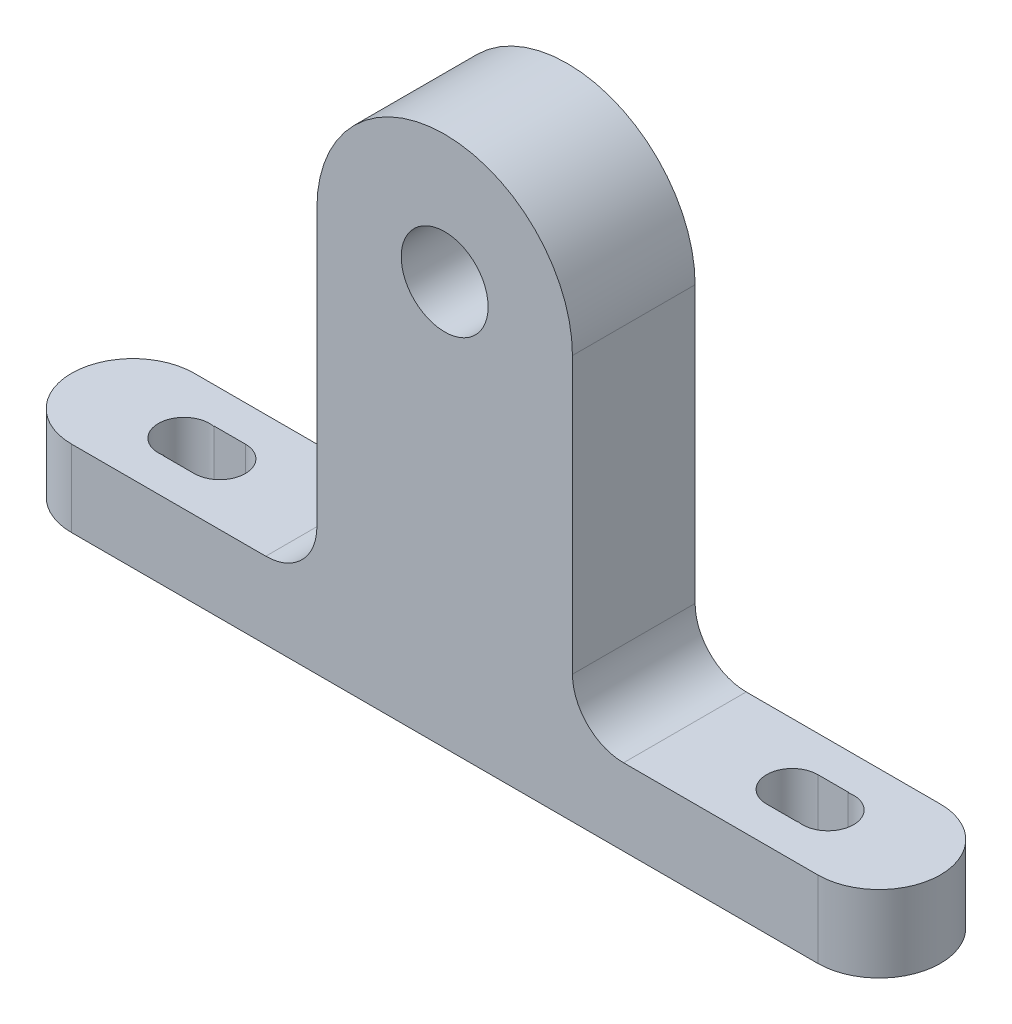
SolidWorks part; units mm, degrees
ref_plane "Front Plane" through (0, 0, 0) normal (0, 0, 1) x (1, 0, 0)
ref_plane "Top Plane" through (0, 0, 0) normal (0, 1, 0) x (1, 0, 0)
ref_plane "Right Plane" through (0, 0, 0) normal (1, 0, 0) x (0, 0, -1)
sketch "Sketch1" plane through (0, 0, 0) normal (0, 0, 1) x (1, 0, 0)
  line L0 (-42.5, -39.5) -> (42.5, -39.5)
  line L1 (42.5, -39.5) -> (42.5, -32)
  line L2 (42.5, -32) -> (12.5, -32)
  line L3 (12.5, -32) -> (12.5, 0)
  line L4 (-42.5, -39.5) -> (-42.5, -32)
  line L5 (-42.5, -32) -> (-12.5, -32)
  line L6 (-12.5, -32) -> (-12.5, 0)
  line L7 (0, -39.5) -> (0, 0) construction
  line L8 (0, 0) -> (0, 12.5) construction
  circle A0 centre (0, 0) radius 12.5
  circle A1 centre (0, 0) radius 4.25
  dimension "D1" = 25
  dimension "D5" = 8.5
  dimension "D2" = 7.5
  dimension "D3" = 85
  dimension "D4" = 52
extrude "Boss-Extrude1" add sketch "Sketch1" along normal blind 6 and the other way blind 6 contours A0 A1 | A0 L6 L5 L4 L0 L1 L2 L3 region at (0, -28.764, 0) region at (0, 12.1464, 0)
sketch "Sketch4" plane through (0, 0, 0) normal (0, 1, 0) x (1, 0, 0)
  line L0 (31.5, -2.5) -> (28, -2.5)
  line L1 (31.5, 2.5) -> (28, 2.5)
  line L2 (-31.5, -2.5) -> (-28, -2.5)
  line L3 (-31.5, 2.5) -> (-28, 2.5)
  line L4 (31.5, 0) -> (28, 0) construction
  line L5 (28, 0) -> (-28, 0) construction
  line L6 (-28, 0) -> (-31.5, 0) construction
  line L7 (29.75, 0) -> (29.75, -6) construction
  line L8 (42.5, -6) -> (12.5, -6) construction
  line L9 (29.75, 0) -> (29.75, 6) construction
  line L10 (42.5, 6) -> (12.5, 6) construction
  line L12 (42.5, 6) -> (42.5, -6) construction
  line L13 (-42.5, -6) -> (-12.5, -6) construction
  line L14 (-42.5, 6) -> (-12.5, 6) construction
  line L15 (-42.5, 6) -> (-42.5, -6) construction
  line L17 (42.5, -6) -> (-42.5, -6)
  line L18 (42.5, -6) -> (42.5, 6)
  line L19 (42.5, 6) -> (-42.5, 6)
  line L20 (-42.5, -6) -> (-42.5, 6)
  circle A0 centre (31.5, 0) radius 2.5
  circle A1 centre (28, 0) radius 2.5
  circle A2 centre (-28, 0) radius 2.5
  circle A3 centre (-31.5, 0) radius 2.5
  circle A5 centre (36.5, 0) radius 6
  circle A6 centre (-36.5, 0) radius 6
  dimension "D1" = 5
  dimension "D3" = 5
  dimension "D2" = 3.5
extrude "Cut-Extrude1" cut sketch "Sketch4" against normal through all contours A5 L17 L18 | A5 L18 L19 | A0 A5 | A5 A1 A0 | A5 A0 A1 L0 | A1 A0 | A0 A1 | A5 A0 A1 | A5 L1 A1 A0 | A6 L2 A2 A3 | A6 A3 A2 | A3 A6 | A2 A3 | A6 A2 A3 | A3 A2 | A6 A3 A2 L3 | A6 L19 L20 | A6 L20 L17 region at (32.1231, 0, 0) region at (29.7378, 0, 2.2904) region at (30.4136, 0, 1.6492) region at (27.5945, 0, 0) region at (41.1598, 0, 4.6598) region at (29.75, 0, 0) region at (30.4136, 0, -1.6492) region at (29.7378, 0, -2.2904) region at (-41.1598, 0, 4.6598) region at (41.1598, 0, -4.6598) region at (-41.1598, 0, -4.6598) region at (-29.7378, 0, 2.2904) region at (-32.1231, 0, 0) region at (-27.5945, 0, 0) region at (-30.4136, 0, 1.6492) region at (-29.7378, 0, -2.2904) region at (-29.75, 0, 0) region at (-30.4136, 0, -1.6492)
fillet "Fillet1" radius 5 2 edges at (-12.5, -32, 0) (12.5, -32, 0)
